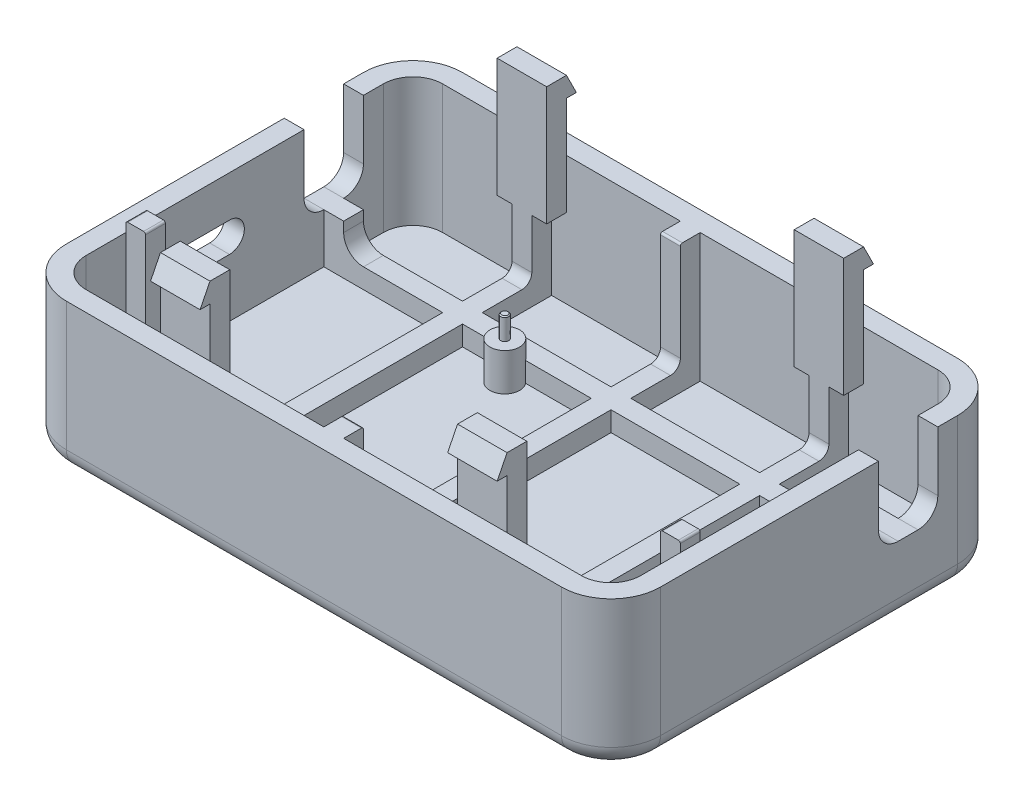
SolidWorks part; units mm, degrees
note: The reader was unsure of these and kept them because the rebuilt part matched: shared geometry of "草图4<2>".
ref_plane "前视基准面" through (0, 0, 0) normal (0, 0, 1) x (1, 0, 0)
ref_plane "上视基准面" through (0, 0, 0) normal (0, 1, 0) x (1, 0, 0)
ref_plane "右视基准面" through (0, 0, 0) normal (1, 0, 0) x (0, 0, -1)
sketch "草图1" plane through (0, 0, 0) normal (0, 1, 0) x (1, 0, 0)
  line L1 (-30, 20) -> (30, 20)
  line L2 (-30, 20) -> (-30, -20)
  line L3 (-30, -20) -> (30, -20)
  line L4 (30, 20) -> (30, -20)
  line L5 (-30, 20) -> (30, -20) construction
  line L6 (-30, -20) -> (30, 20) construction
  point P0 (0, 0)
  dimension "D1" = 60
  dimension "D2" = 40
extrude "凸台-拉伸1" add sketch "草图1" along normal blind 15
fillet "圆角1" radius 5 4 edges at (30, 7.5, -20) (30, 7.5, 20) (-30, 7.5, -20) (-30, 7.5, 20)
fillet "圆角2" radius 2 8 edges at (-28.5355, 0, -18.5355) (-30, 0, 0) (-28.5355, 0, 18.5355) (0, 0, 20) (28.5355, 0, 18.5355) (30, 0, 0) (28.5355, 0, -18.5355) (0, 0, -20)
shell "抽壳1" thickness 2
sketch "草图3" plane through (0, 0, 0) normal (1, 0, 0) x (0, 0, -1)
  line L0 (-16, 14.8) -> (-16, 5)
  line L1 (-15, 15) -> (-18, 15) construction
  line L2 (-15, 4) -> (15, 4)
  line L3 (16, 5) -> (16, 14.8)
  line L4 (18, 15) -> (15, 15) construction
  line L5 (16.2, 15) -> (18, 15)
  line L6 (18, 15) -> (18, 2)
  line L7 (18, 2) -> (-18, 2)
  line L8 (-18, 2) -> (-18, 15)
  line L9 (-18, 15) -> (-16.2, 15)
  arc A0 (16, 5) -> (15, 4) centre (15, 5) cw
  arc A1 (-15, 4) -> (-16, 5) centre (-15, 5) cw
  arc A2 (16.2, 15) -> (16, 14.8) centre (16.2, 14.8) ccw
  arc A3 (-16, 14.8) -> (-16.2, 15) centre (-16.2, 14.8) ccw
  point P22 (16, 15)
  point P25 (-16, 15)
  dimension "D4" = 1
  dimension "D5" = 0.2
  dimension "D1" = 2
  dimension "D2" = 2
  dimension "D3" = 2
extrude "凸台-拉伸2" add sketch "草图3" along normal mid plane 2
pattern_linear "阵列(线性)1" count 2 spacing 15 along (-1, 0, 0) count 2 spacing 15 along (1, 0, 0) of "凸台-拉伸2"
ref_plane "基准面1" through (0, 0, 10) normal (0, 0, 1) x (1, 0, 0)
sketch "草图4" plane through (0, 0, 0) normal (0, 0, 1) x (1, 0, 0)
  line L0 (-27.8, 16) -> (-26.2, 16)
  line L1 (-25, 15) -> (-28, 15) construction
  line L2 (-28, 15.8) -> (-28, 2)
  line L3 (-28, 2) -> (28, 2)
  line L4 (28, 2) -> (28, 15.8)
  line L5 (27.8, 16) -> (26.2, 16)
  line L6 (28, 15) -> (25, 15) construction
  line L7 (26, 15.8) -> (26, 6)
  line L8 (24, 4) -> (-24, 4)
  line L9 (-26, 6) -> (-26, 15.8)
  line L10 (-25, 15) -> (-30, 15) construction
  line L11 (30, 15) -> (25, 15) construction
  arc A0 (-27.8, 16) -> (-28, 15.8) centre (-27.8, 15.8) ccw
  arc A1 (-26.2, 16) -> (-26, 15.8) centre (-26.2, 15.8) cw
  arc A2 (26, 6) -> (24, 4) centre (24, 6) cw
  arc A3 (-24, 4) -> (-26, 6) centre (-24, 6) cw
  arc A4 (26.2, 16) -> (26, 15.8) centre (26.2, 15.8) ccw
  arc A5 (27.8, 16) -> (28, 15.8) centre (27.8, 15.8) cw
  point P18 (26, 15)
  point P21 (-26, 15)
  dimension "D4" = 1
  dimension "D5" = 2
  dimension "D7" = 0.2
  dimension "D1" = 2
  dimension "D2" = 2
  dimension "D3" = 2
  dimension "D6" = 1
extrude "凸台-拉伸3" add sketch "草图4" along normal mid plane 2 from surface at 10 starting at plane "基准面1"
ref_plane "基准面2" through (0, 0, -10) normal (0, 0, 1) x (1, 0, 0)
extrude "凸台-拉伸4" add sketch "草图4<2>" along normal mid plane 2 from surface at -10 starting at plane "基准面2"
sketch "草图4<2>" plane through (0, 0, 0) normal (0, 0, 1) x (1, 0, 0) same geometry as "草图4"
sketch "草图5" plane through (-30, 0, 0) normal (-1, 0, 0) x (0, 0, 1)
  line L0 (4.5282, 9.35) -> (0.5282, 9.35) construction
  line L1 (4.5282, 7.85) -> (0.5282, 7.85)
  line L2 (4.5282, 10.85) -> (0.5282, 10.85)
  line L4 (0.5282, 8.35) -> (4.5282, 8.35) construction
  arc A0 (4.5282, 7.85) -> (4.5282, 10.85) centre (4.5282, 9.35) ccw
  arc A1 (0.5282, 10.85) -> (0.5282, 7.85) centre (0.5282, 9.35) ccw
  point P4 (2.5282, 9.35)
  dimension "D1" = 0.5
extrude "切除-拉伸1" cut sketch "草图5" against normal up to next
sketch "草图6" plane through (0, 2, 0) normal (0, 1, 0) x (1, 0, 0)
  circle A0 centre (-21.8497, -12.1013) radius 2
  circle A1 centre (22.0613, -11.9743) radius 2
  circle A2 centre (-8.8017, 8.0737) radius 1.5
  dimension "D1" = 4
  dimension "D2" = 4
  dimension "D3" = 3
extrude "凸台-拉伸5" add sketch "草图6" along normal blind 3.8
sketch "草图7" plane through (0, 5.8, 0) normal (0, 1, 0) x (1, 0, 0)
  circle A0 centre (-21.8497, -12.1013) radius 1.4
  circle A1 centre (-8.8017, 8.0737) radius 0.4
  circle A2 centre (22.0613, -11.9743) radius 1.4
  dimension "D1" = 2.8
  dimension "D2" = 0.8
  dimension "D3" = 2.8
extrude "凸台-拉伸6" add sketch "草图7" along normal blind 2.2
chamfer "倒角1" distance 0.1 angle 45 1 edges at (-8.8017, 8, -7.6737)
chamfer "倒角2" distance 0.2 angle 45 2 edges at (-21.8497, 8, 13.5013) (22.0613, 8, 13.3743)
sketch "草图8" plane through (0, 0, -18) normal (0, 0, 1) x (1, 0, 0)
  line L0 (-15, 14.8) -> (-15, 20.3138) construction
  line L1 (-14, 14.8) -> (-16, 14.8) construction
  line L4 (-1, 15) -> (-14, 15) construction
  line L5 (-17.5, 22) -> (-12.5, 22)
  line L6 (-17.5, 22) -> (-17.5, 10)
  line L7 (-17.5, 10) -> (-12.5, 10)
  line L8 (-12.5, 22) -> (-12.5, 10)
  line L9 (-17.5, 22) -> (-12.5, 10) construction
  line L10 (-17.5, 10) -> (-12.5, 22) construction
  point P8 (-15, 16)
  dimension "D1" = 5
  dimension "D2" = 5
  dimension "D3" = 12
extrude "凸台-拉伸7" add sketch "草图8" along normal blind 2
sketch "草图9" plane through (-17.5, 0, 0) normal (-1, 0, 0) x (0, 0, 1)
  line L0 (-18, 22) -> (-19, 20)
  line L1 (-19, 20) -> (-18, 20)
  line L2 (-18, 22) -> (-18, 15) construction
  line L3 (-18, 20) -> (-18, 22)
  dimension "D1" = 2
  dimension "D2" = 1
extrude "凸台-拉伸8" add sketch "草图9" against normal up to surface (5 mm away) up to face at (-12.5, 15.8, -17.2)
mirror "镜向2" about plane through (0, 0, 0) normal (1, 0, 0) of "凸台-拉伸8", "凸台-拉伸7"
mirror "镜向3" about plane through (0, 0, 0) normal (0, 0, 1) of "镜向2", "凸台-拉伸8", "凸台-拉伸7"
sketch "草图10" plane through (-30, 0, 0) normal (-1, 0, 0) x (0, 0, 1)
  line L1 (-13, 17) -> (-7, 17)
  line L2 (-13, 17) -> (-13, 9)
  line L3 (-11, 7) -> (-9, 7)
  line L4 (-7, 17) -> (-7, 9)
  line L6 (-20, 2) -> (-20, 15) construction
  line L7 (-15, 15) -> (15, 15) construction
  arc A0 (-7, 9) -> (-9, 7) centre (-9, 9) cw
  arc A1 (-11, 7) -> (-13, 9) centre (-11, 9) cw
  point P10 (-7, 7)
  point P13 (-13, 7)
  dimension "D5" = 2
  dimension "D1" = 8
  dimension "D2" = 7
  dimension "D3" = 6
  dimension "D4" = 2
extrude "切除-拉伸4" cut sketch "草图10" against normal blind 10
mirror "镜向4" about plane through (0, 0, 0) normal (1, 0, 0) of "切除-拉伸4"
